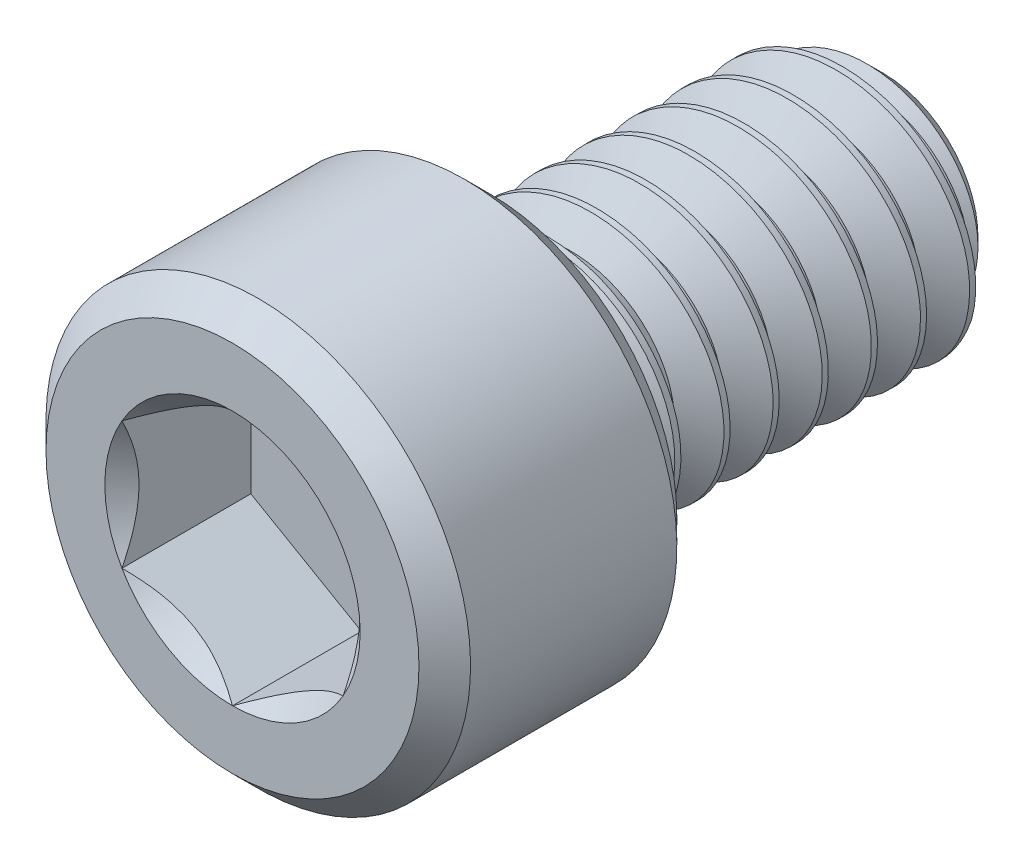
SolidWorks part; units mm, degrees
ref_plane "Front Plane" through (0, 0, 0) normal (0, 0, 1) x (1, 0, 0)
ref_plane "Top Plane" through (0, 0, 0) normal (0, 1, 0) x (1, 0, 0)
ref_plane "Right Plane" through (0, 0, 0) normal (1, 0, 0) x (0, 0, -1)
sketch "Sketch1" plane through (0, 0, 0) normal (1, 0, 0) x (0, 0, -1)
  line L0 (5.2578, 0) -> (-5.2578, 0) construction
  line L1 (-5.2578, 0) -> (-5.2578, 3.0124)
  line L2 (-5.2578, 3.0124) -> (-4.8412, 3.429)
  line L3 (-4.8412, 3.429) -> (-1.5088, 3.429)
  line L4 (-1.5088, 3.429) -> (-1.0922, 3.0124)
  line L5 (-1.0922, 3.0124) -> (-1.0922, 2.0828)
  line L6 (-1.0922, 2.0828) -> (4.7022, 2.0828)
  line L7 (4.7022, 2.0828) -> (5.2578, 1.5272)
  line L8 (5.2578, 1.5272) -> (5.2578, 0)
  line L9 (5.2082, 2.1687) -> (6.0019, 2.1687) construction
  line L10 (6.0019, 2.1687) -> (5.6051, 1.4813) construction
  line L11 (5.6051, 1.4813) -> (5.2082, 2.1687) construction
  line L12 (5.2578, 2.0828) -> (5.9523, 2.0828) construction
  line L13 (5.6051, 2.1687) -> (5.6051, 2.0828) construction
  line L14 (5.5555, 1.5672) -> (5.6547, 1.5672) construction
  line L15 (5.6051, 1.5672) -> (5.6051, 1.4813) construction
  line L16 (5.233, 2.1258) -> (5.9771, 2.1258)
  line L17 (5.9771, 2.1258) -> (5.6547, 1.5672)
  line L18 (5.6547, 1.5672) -> (5.5555, 1.5672)
  line L19 (5.5555, 1.5672) -> (5.233, 2.1258)
  line L20 (4.7022, -2.0828) -> (3.2734, -2.0828) construction
  point P4 (0, 0)
  point P25 (5.6051, 2.1258)
  point P26 (5.2578, 2.0828)
  point P33 (3.2734, -2.0828)
  dimension "Head Ht" = 4.1656
  dimension "Screw Size" = 4.1656
  dimension "Head Dia" = 6.858
  dimension "D1" = 45
  dimension "D2" = 45
  dimension "D3" = 0.4166
  dimension "D4" = 0.4166
  dimension "Pitch" = 0.7937
  dimension "D5" = 0.0992
  dimension "D6" = 0.5556
  dimension "D7" = 1.4287
  dimension "Length" = 6.35
sketch "Sketch2" plane through (0, 0, 0) normal (0, 0, 1) x (1, 0, 0)
  line L1 (0, 2.0622) -> (-1.7859, 1.0311)
  line L2 (-1.7859, 1.0311) -> (-1.7859, -1.0311)
  line L3 (-1.7859, -1.0311) -> (0, -2.0622)
  line L4 (0, -2.0622) -> (1.7859, -1.0311)
  line L5 (1.7859, -1.0311) -> (1.7859, 1.0311)
  line L6 (1.7859, 1.0311) -> (0, 2.0622)
  circle A0 centre (0, 0) radius 1.7859 construction
  circle A1 centre (0, 0) radius 3.429
  point P1 (0, 3.429)
  dimension "D1" = 6.858
  dimension "Drive Size" = 3.5719
sketch "Sketch3" plane through (0, 0, 0) normal (1, 0, 0) x (0, 0, -1)
  line L0 (5.2578, 0) -> (-5.2578, 0) construction
  line L1 (-5.2578, 0) -> (-5.2578, 3.0124) construction
  line L2 (-5.2578, 3.0124) -> (-4.8412, 3.429) construction
  line L3 (-4.8412, 3.429) -> (-1.5088, 3.429) construction
  line L4 (-1.5088, 3.429) -> (-1.0922, 3.0124) construction
  line L5 (-1.0922, 3.0124) -> (-1.0922, 2.0828) construction
  line L6 (-1.0922, 2.0828) -> (4.7022, 2.0828) construction
  line L7 (4.7022, 2.0828) -> (5.2578, 1.5272) construction
  line L8 (5.2578, 1.5272) -> (5.2578, 0) construction
  line L9 (5.2578, 0) -> (-5.2578, 0)
  line L10 (-5.2578, 0) -> (-5.2578, 3.0124)
  line L11 (-5.2578, 3.0124) -> (-4.8412, 3.429)
  line L12 (-4.8412, 3.429) -> (-1.5088, 3.429)
  line L13 (-1.5088, 3.429) -> (-1.0922, 3.0124)
  line L14 (-1.0922, 3.0124) -> (-1.0922, 2.0828)
  line L15 (-1.0922, 2.0828) -> (4.7022, 2.0828)
  line L16 (4.7022, 2.0828) -> (5.2578, 1.5272)
  line L17 (5.2578, 1.5272) -> (5.2578, 0)
revolve "Revolve1" add sketch "Sketch3" angle 360 about L0
sketch "Sketch4" plane through (0, 0, 5.2578) normal (0, 0, 1) x (1, 0, 0)
  line L0 (0, -2.0622) -> (1.7859, -1.0311) construction
  line L1 (1.7859, -1.0311) -> (1.7859, 1.0311) construction
  line L2 (1.7859, 1.0311) -> (0, 2.0622) construction
  line L3 (0, 2.0622) -> (-1.7859, 1.0311) construction
  line L4 (-1.7859, 1.0311) -> (-1.7859, -1.0311) construction
  line L5 (-1.7859, -1.0311) -> (0, -2.0622) construction
  line L6 (0, -2.0622) -> (1.7859, -1.0311)
  line L7 (1.7859, -1.0311) -> (1.7859, 1.0311)
  line L8 (1.7859, 1.0311) -> (0, 2.0622)
  line L9 (0, 2.0622) -> (-1.7859, 1.0311)
  line L10 (-1.7859, 1.0311) -> (-1.7859, -1.0311)
  line L11 (-1.7859, -1.0311) -> (0, -2.0622)
extrude "Cut-Extrude1" cut sketch "Sketch4" against normal blind 2.0828
sketch "Sketch5" plane through (0, 0, 5.2578) normal (0, 0, 1) x (1, 0, 0)
  circle A0 centre (0, 0) radius 2.0622
extrude "Cut-Extrude3" cut sketch "Sketch5" against normal through all draft 45
split "Split1" bodies to split 107 resulting bodies 108 109 split by face at (0, 3.0124, 1.0922)
sketch "Sketch6" plane through (0, 0, -5.2578) normal (0, 0, -1) x (-1, 0, 0)
  circle A0 centre (0, 0) radius 2.0828 construction
  circle A1 centre (0, 0) radius 2.0828
curve "Helix/Spiral1" pitch 0.7937 height 7.1437 radius 2.0828 centre (0, 0, -5.2578) axis (0, 0, 1) start towards (0, 1, 0)
sketch "Sketch7" plane through (0, 0, 0) normal (1, 0, 0) x (0, 0, -1)
  line L0 (5.233, 2.1258) -> (5.9771, 2.1258) construction
  line L1 (5.9771, 2.1258) -> (5.6547, 1.5672) construction
  line L2 (5.6547, 1.5672) -> (5.5555, 1.5672) construction
  line L3 (5.5555, 1.5672) -> (5.233, 2.1258) construction
  line L4 (5.233, 2.1258) -> (5.9771, 2.1258)
  line L5 (5.9771, 2.1258) -> (5.6547, 1.5672)
  line L6 (5.6547, 1.5672) -> (5.5555, 1.5672)
  line L7 (5.5555, 1.5672) -> (5.233, 2.1258)
sweep "Cut-Sweep1" cut profiles "Sketch7" path "Helix/Spiral1" align with end faces yes
sketch "Sketch8" plane through (0, 0, 1.0922) normal (0, 0, -1) x (-1, 0, 0)
  circle A1 centre (0, 0) radius 2.0828
extrude "Boss-Extrude1" add sketch "Sketch8" along normal up to next (6.35 mm away) draft 20
equation "\"D3@Sketch1\"=\"Head Ht@Sketch1\"/10"
equation "\"D4@Sketch1\"=\"Head Ht@Sketch1\"/10"
equation "\"D5@Sketch1\"=\"Pitch@Sketch1\"/8"
equation "\"D6@Sketch1\"=\"Pitch@Sketch1\"*.7"
equation "\"D7@Sketch1\"=\"Pitch@Sketch1\"*2.5-\"D6@Sketch1\""
equation "\"D1@Cut-Extrude1\"=\"Head Ht@Sketch1\"/2"
equation "\"D4@Helix/Spiral1\"=\"Pitch@Sketch1\""
equation "\"D3@Helix/Spiral1\"=\"Length@Sketch1\"+\"D4@Helix/Spiral1\""
